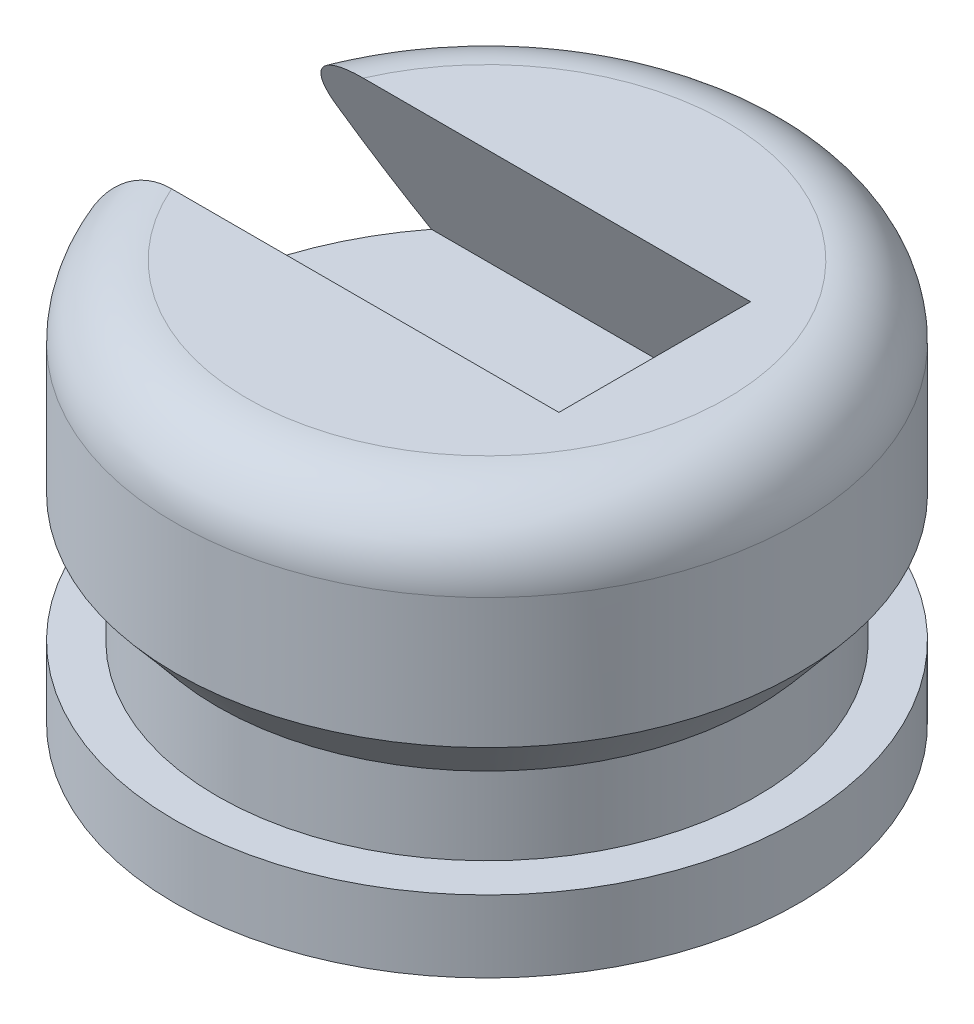
SolidWorks part; units mm, degrees
ref_plane "Front Plane" through (0, 0, 0) normal (0, 0, 1) x (1, 0, 0)
ref_plane "Top Plane" through (0, 0, 0) normal (0, 1, 0) x (1, 0, 0)
ref_plane "Side Plane" through (0, 0, 0) normal (1, 0, 0) x (0, 0, -1)
sketch "Sketch1" plane through (0, 0, 0) normal (0, 1, 0) x (1, 0, 0)
  circle A0 centre (0, 0) radius 13
  dimension "D1" = 26
extrude "Boss-Extrude1" add sketch "Sketch1" along normal blind 3
sketch "Sketch2" plane through (0, 3, 0) normal (0, 1, 0) x (1, 0, 0)
  circle A0 centre (0, 0) radius 11.25
  dimension "D1" = 22.5
extrude "Boss-Extrude2" add sketch "Sketch2" along normal blind 1.75
sketch "Sketch3" plane through (0, 4.75, 0) normal (0, 1, 0) x (1, 0, 0)
  circle A0 centre (0, 0) radius 13
  dimension "D1" = 26
extrude "Boss-Extrude4" add sketch "Sketch3" along normal blind 12
sketch "Sketch4" plane through (0, 0, 0) normal (1, 0, 0) x (0, 0, -1)
  line L1 (13, 16.75) -> (-13, 16.75) construction
  line L2 (-0.0409, 8.75) -> (-8.0409, 8.75)
  line L3 (-8.0409, 8.75) -> (-4, 16.75)
  line L4 (-4, 16.75) -> (0, 16.75)
  line L5 (-0.0409, 8.75) -> (7.9591, 8.75)
  line L6 (7.9591, 8.75) -> (4, 16.75)
  line L7 (4, 16.75) -> (0, 16.75)
  dimension "D1" = 16
  dimension "D2" = 8
  dimension "D3" = 4
  dimension "D4" = 8
  dimension "D5" = 8
extrude "Cut-Extrude1" cut sketch "Sketch4" against normal through all and the other way blind 7
chamfer "Chamfer1" distance 3 angle 50 1 edges at (0, 4.75, 13) first distance on face at (0, 4.75, 13)
fillet "Fillet1" radius 3 1 edges at (13, 16.75, 0) tangent propagation no
